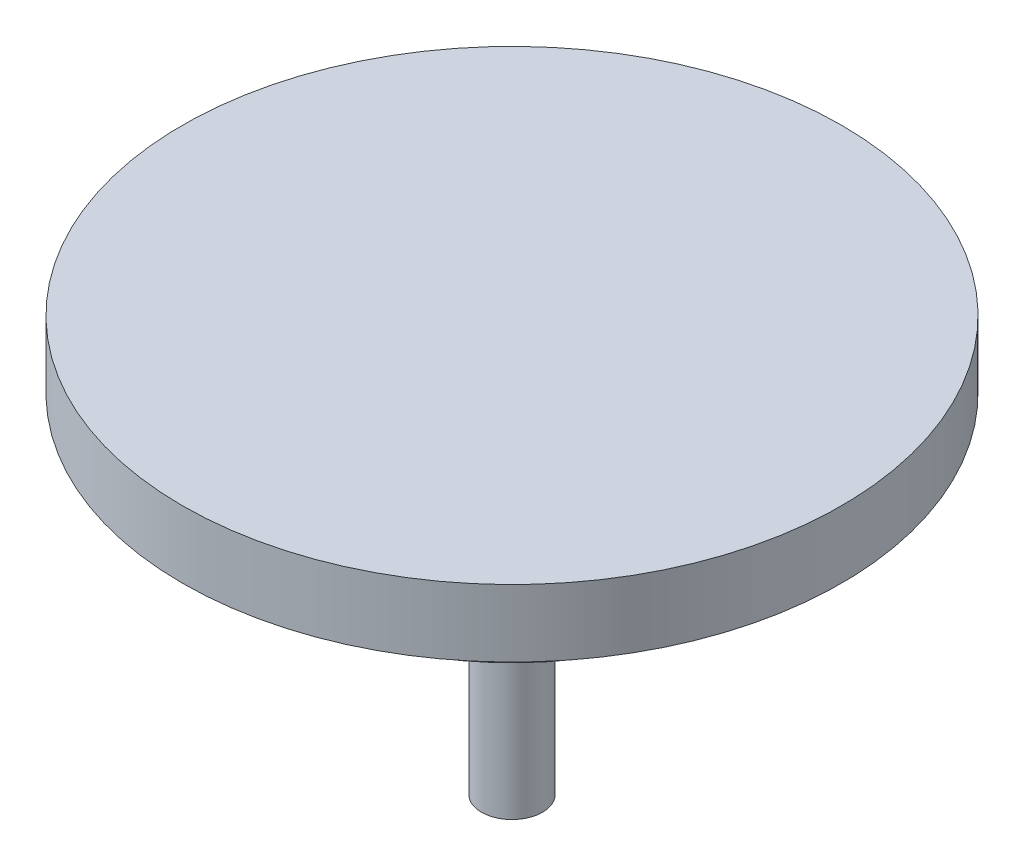
SolidWorks part; units mm, degrees
ref_plane "Front Plane" through (0, 0, 0) normal (0, 0, 1) x (1, 0, 0)
ref_plane "Top Plane" through (0, 0, 0) normal (0, 1, 0) x (1, 0, 0)
ref_plane "Right Plane" through (0, 0, 0) normal (1, 0, 0) x (0, 0, -1)
sketch "Sketch2" plane through (0, 0, 0) normal (0, 1, 0) x (1, 0, 0)
  circle A0 centre (0, 0) radius 54
  circle A1 centre (0, 0) radius 5
  dimension "D1" = 108
  dimension "D2" = 10
extrude "Boss-Extrude2" add sketch "Sketch2" against normal blind 57 contours A1 region at (0, 0, 0)
extrude "Boss-Extrude4" add sketch "Sketch2<5>" along normal blind 11 contours A0
sketch "Sketch2<5>" plane through (0, 0, 0) normal (0, 1, 0) x (1, 0, 0) same geometry as "Sketch2"
sketch "Sketch3" plane through (0, 0, 0) normal (0, -1, 0) x (1, 0, 0)
  line L0 (0, 0) -> (-64.4312, 0) construction
  line L1 (0, 55.8183) -> (0, 0) construction
  line L2 (0, 0) -> (0, -59.2532) construction
  circle A0 centre (-46, 19) radius 4
  arc A1 (-28.5657, -28) -> (0, 40) centre (0, 0) ccw
  spline S0 degree 2 poles (-28.5657, -28) (-4.3591, 1.6357) (0, 40) knots 0 0 0 1 1 1
  dimension "D1" = 11
  dimension "D3" = 8
  dimension "D4" = 80
  dimension "D5" = 28
  dimension "D2" = 46
  dimension "D7" = 19
extrude "Boss-Extrude6" add sketch "Sketch3" along normal blind 10
